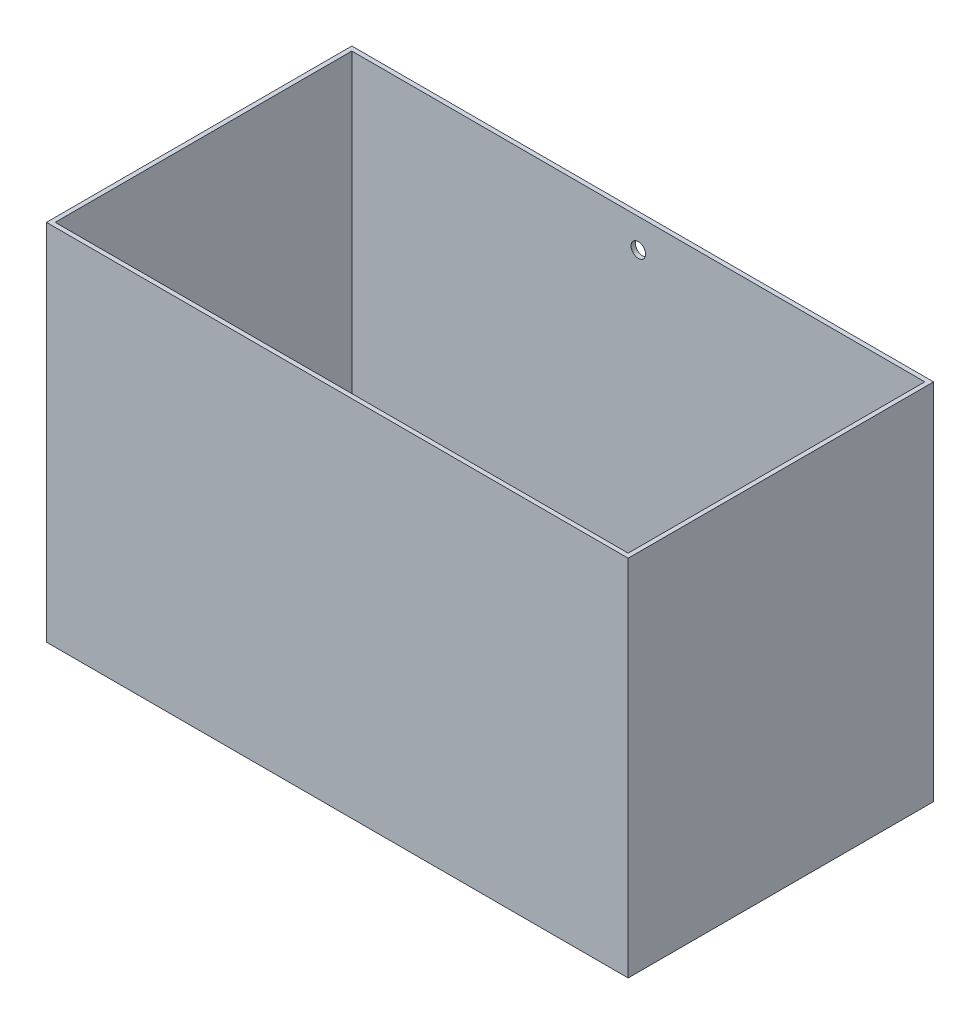
SolidWorks part; units mm, degrees
ref_plane "Front Plane" through (0, 0, 0) normal (0, 0, 1) x (1, 0, 0)
ref_plane "Top Plane" through (0, 0, 0) normal (0, 1, 0) x (1, 0, 0)
ref_plane "Right Plane" through (0, 0, 0) normal (1, 0, 0) x (0, 0, -1)
sketch "Sketch1" plane through (0, 0, 0) normal (0, 1, 0) x (1, 0, 0)
  line L1 (0, 0) -> (400, 0)
  line L2 (0, 0) -> (0, -210)
  line L3 (0, -210) -> (400, -210)
  line L4 (400, 0) -> (400, -210)
  dimension "D1" = 400
  dimension "D2" = 210
extrude "Extrude-Thin1" add sketch "Sketch1" along normal blind 250 thin thin type one direction reverse wall 3
sketch "Sketch4" plane through (0, 0, 0) normal (0, 0, -1) x (-1, 0, 0)
  line L0 (-400, 250) -> (0, 250) construction
  line L1 (-400, 250) -> (-400, 0) construction
  circle A0 centre (-200, 230) radius 5
  dimension "D2" = 10
  dimension "D3" = 200
  dimension "D1" = 20
extrude "Cut-Extrude1" cut sketch "Sketch4" against normal blind 10
